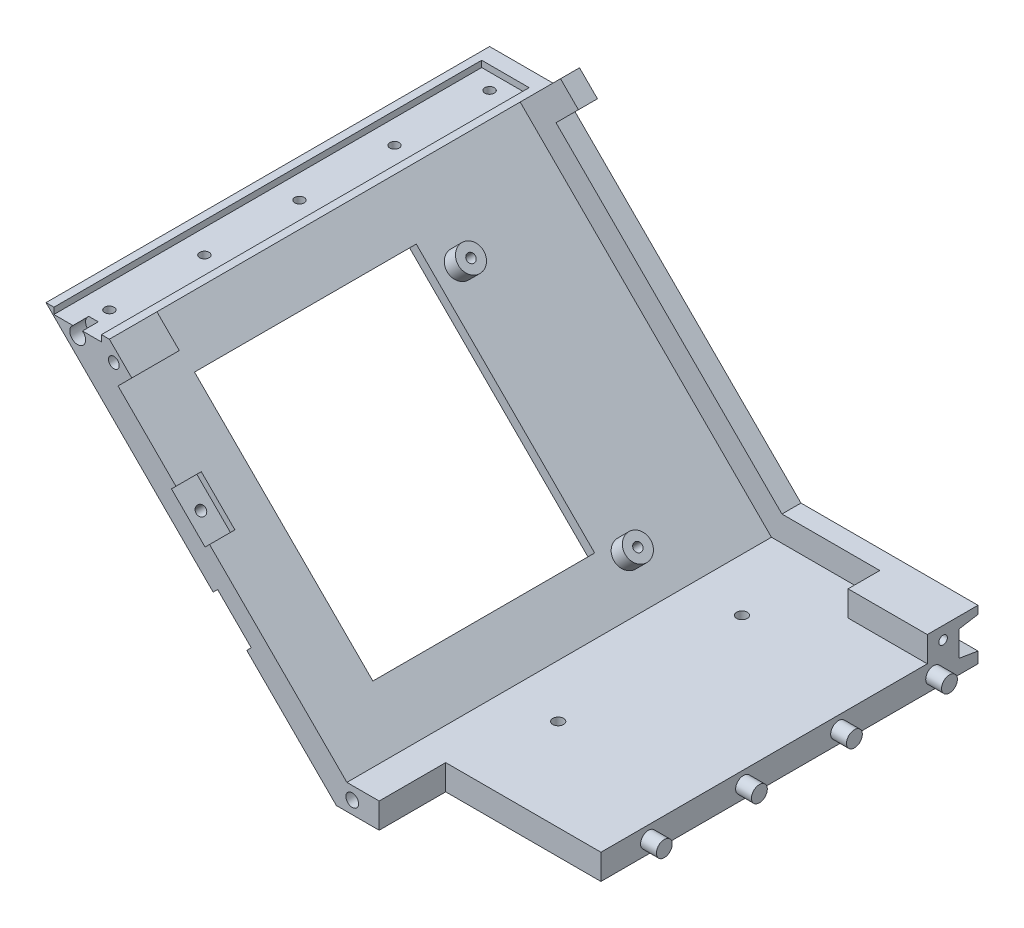
SolidWorks part; units mm, degrees
ref_plane "Plan de face" through (0, 0, 0) normal (0, 0, 1) x (1, 0, 0)
ref_plane "Plan de dessus" through (0, 0, 0) normal (0, 1, 0) x (1, 0, 0)
ref_plane "Plan de droite" through (0, 0, 0) normal (1, 0, 0) x (0, 0, -1)
sketch "Main-Sketch" plane through (0, 0, 0) normal (0, 0, 1) x (1, 0, 0)
  line L0 (0, 0) -> (0, 8)
  line L1 (0, 8) -> (-59.1863, 8)
  line L2 (-59.1863, 8) -> (-138.4931, 87.3069)
  line L3 (-154.15, 91.65) -> (-134.15, 91.65)
  line L4 (-154.15, 91.65) -> (-62.5, 0)
  line L5 (-62.5, 0) -> (0, 0)
  line L8 (-134.15, 91.65) -> (-138.4931, 87.3069)
  dimension "D1" = 8
  dimension "D2" = 8
  dimension "D3" = 62.5
  dimension "D4" = 135
  dimension "D5" = 20
  dimension "D6" = 154.15
extrude "Main-Extrusion" add sketch "Main-Sketch" along normal blind 140
sketch "Lcd-Sketch" plane through (0, 0, 0) normal (0, -1, 0) x (1, 0, 0)
  line L1 (0, 140) -> (-49, 140)
  line L2 (0, 140) -> (0, 119)
  line L3 (0, 119) -> (-49, 119)
  line L4 (-49, 140) -> (-49, 119)
  dimension "D1" = 21
  dimension "D2" = 49
extrude "Lcd-Hole" cut sketch "Lcd-Sketch" against normal through all
sketch "MotorBoard-Hole-Sketch" plane through (-31.25, -31.25, 0) normal (-0.7071, -0.7071, 0) x (0, 0, 1)
  line L0 (0, 173.8068) -> (0, 44.1942) construction
  line L1 (120, 143.8068) -> (50, 143.8068)
  line L2 (120, 143.8068) -> (120, 64.1942)
  line L3 (120, 64.1942) -> (50, 64.1942)
  line L4 (50, 143.8068) -> (50, 64.1942)
  line L5 (140, 173.8068) -> (140, 44.1942) construction
  line L6 (140, 173.8068) -> (0, 173.8068) construction
  line L7 (140, 44.1942) -> (0, 44.1942) construction
  dimension "D1" = 50
  dimension "D2" = 20
  dimension "D3" = 30
  dimension "D4" = 20
extrude "MotorBoard-Hole" cut sketch "MotorBoard-Hole-Sketch" against normal through all
sketch "MotorBoard-Window-Sketch" plane through (-31.25, -31.25, 0) normal (-0.7071, -0.7071, 0) x (0, 0, 1)
  line L0 (120, 64.1942) -> (120, 143.8068) construction
  line L1 (128, 151.8068) -> (42, 151.8068)
  line L2 (128, 151.8068) -> (128, 56.1942)
  line L3 (128, 56.1942) -> (42, 56.1942)
  line L4 (42, 151.8068) -> (42, 56.1942)
  line L5 (120, 143.8068) -> (50, 143.8068) construction
  line L6 (50, 143.8068) -> (50, 64.1942) construction
  line L7 (50, 64.1942) -> (120, 64.1942) construction
  dimension "D1" = 8
  dimension "D2" = 8
  dimension "D3" = 8
  dimension "D4" = 8
extrude "MotorBoard-Window" cut sketch "MotorBoard-Window-Sketch" against normal blind 5
sketch "MotorBoard-Fix-Sketch" plane through (-25.5931, -25.5931, 0) normal (0.7071, 0.7071, 0) x (0, 0, -1)
  line L0 (-140, 47.5079) -> (-140, 159.6647) construction
  line L1 (-140, 47.5079) -> (0, 47.5079) construction
  circle A0 centre (-42.5, 60.5079) radius 4
  circle A1 centre (-42.5, 135.0079) radius 4
  dimension "D1" = 8
  dimension "D2" = 74.5
  dimension "D3" = 97.5
  dimension "D4" = 13
extrude "MotorBoard-Fix-Extrusion" add sketch "MotorBoard-Fix-Sketch" along normal blind 5
sketch "MotorBoard-Fix-Hole-Sketch" plane through (-22.0576, -22.0576, 0) normal (0.7071, 0.7071, 0) x (0, 0, -1)
  circle A0 centre (-42.5, 60.5079) radius 1.35
  circle A1 centre (-42.5, 135.0079) radius 1.35
  circle A2 centre (-42.5, 135.0079) radius 4 construction
  dimension "D1" = 2.7
extrude "MotorBoard-Fix-Hole" cut sketch "MotorBoard-Fix-Hole-Sketch" against normal through all
hole_wizard "Fraisage pour vis à tête fraisée M32" positions "Esquisse8" profile "Esquisse9" countersink size "M3" standard "Ansi Metric" end condition through all
sketch "Esquisse8" plane through (0, 0, 0) normal (0, -1, 0) x (-1, 0, 0)
  line L2 (62.5, -140) -> (49, -140) construction
  line L4 (62.5, -140) -> (62.5, 0) construction
  line L5 (0, -119) -> (0, 0) construction
  point P0 (42.5, -90)
  point P2 (42.5, -32)
  dimension "D1" = 58
  dimension "D2" = 20
  dimension "D3" = 50
  dimension "D4" = 42.5
sketch "Esquisse9" plane through (-42.5, 0, 90) normal (1, 0, 0) x (0, 0, -1)
  line L0 (0, 0) -> (0, 91.65)
  line L1 (0, 91.65) -> (1.7, 91.65)
  line L2 (1.7, 91.65) -> (1.7, 1.45)
  line L3 (1.7, 1.45) -> (3.15, 0)
  line L5 (3.15, 0) -> (0, 0)
  line L6 (-1.7, 1.45) -> (-3.15, 0) construction
  line L11 (0, -6.35) -> (0, 107.95) construction
  dimension "Diamètre du perçage jusqu'au prochain" = 3.4
  dimension "Profondeur du perçage jusqu'au prochain" = 91.65
  dimension "Diamètre du fraisage entrant" = 6.3
  dimension "Angle du fraisage entrant" = 90
sketch "Bottom-Reinforcement-Sketch" plane through (0, 0, 0) normal (0, 0, -1) x (-1, 0, 0)
  line L0 (0, 8) -> (0, 16)
  line L1 (0, 16) -> (55.8726, 16)
  line L2 (55.8726, 16) -> (127.1794, 87.3069)
  line L3 (127.1794, 87.3069) -> (120.1084, 94.3779)
  line L4 (120.1084, 94.3779) -> (125.7652, 100.0348)
  line L5 (125.7652, 100.0348) -> (138.4931, 87.3069)
  line L6 (138.4931, 87.3069) -> (59.1863, 8)
  line L7 (59.1863, 8) -> (0, 8)
  dimension "D1" = 8
  dimension "D2" = 8
  dimension "D3" = 10
  dimension "D4" = 8
extrude "Bottom-Reinforcement-Extrusion" add sketch "Bottom-Reinforcement-Sketch" against normal blind 6 separate body
sketch "LeftFix-Sketch" plane through (0, 0, 0) normal (1, 0, 0) x (0, 0, -1)
  line L0 (0, 0) -> (0, 8) construction
  line L1 (-119, 8) -> (-119, 0) construction
  circle A0 centre (-104, 4) radius 2.5
  point P4 (0, 4)
  dimension "D2" = 5
  dimension "D1" = 15
extrude "LeftFix-Extrusion" add sketch "LeftFix-Sketch" along normal blind 5
pattern_linear "Répétition linéaire1" count 4 spacing 30 along (0, 0, -1) of "LeftFix-Extrusion"
ref_plane "EndOfBottomFix-Plan" through (-15, 0, 0) normal (1, 0, 0) x (0, 0, -1)
ref_axis "EndOfBottomFix-Axe" through (-15, 8, 6) along (0, 1, 0)
ref_plane "EndOfBottomFix-Inclined-Plan" through (-15.4952, 0, 4.1519) normal (0.9659, 0, -0.2588) x (0, 1, 0)
sketch "EndOfBottomFix-Sketch" plane through (0, 0, 0) normal (1, 0, 0) x (0, 0, -1)
  line L0 (0, 3.5) -> (-6, 4.5)
  line L1 (0, 16) -> (0, 8) construction
  line L2 (-6, 4.5) -> (-6, 12.5)
  line L3 (-6, 12.5) -> (0, 13.5)
  line L4 (0, 13.5) -> (0, 3.5)
  line L5 (-6, 16) -> (-6, 8) construction
  dimension "D1" = 2.5
  dimension "D2" = 10
  dimension "D3" = 8
extrude "EndOfBottomFix-Hole" cut sketch "EndOfBottomFix-Sketch" against normal up to surface (16.6077 mm away) up to plane "EndOfBottomFix-Inclined-Plan"
sketch "Bottom-Fix-Reinforcement-Sketch" plane through (0, 8, 0) normal (0, 1, 0) x (1, 0, 0)
  line L1 (0, -6) -> (-25, -6)
  line L2 (0, -6) -> (0, -16)
  line L3 (0, -16) -> (-25, -16)
  line L4 (-25, -6) -> (-25, -16)
  dimension "D1" = 25
  dimension "D2" = 10
extrude "Bottom-Fix-Reinforcement-Extrusion" add sketch "Bottom-Fix-Reinforcement-Sketch" along normal up to surface (8 mm away) up to face at (-27.9363, 16, 3)
sketch "Bottom-Fix-Left-Right-Sketch" plane through (-25, 0, 0) normal (1, 0, 0) x (0, 0, -1)
  line L0 (-16, 16) -> (-16, 8) construction
  line L1 (-6, 16) -> (-16, 16) construction
  circle A0 centre (-11, 12) radius 1.35
  point P4 (-16, 12)
  point P8 (-11, 16)
  dimension "D1" = 2.7
extrude "Bottom-Fix-Left-Right-Hole" cut sketch "Bottom-Fix-Left-Right-Sketch" along normal through all
sketch "Bottom-Top-Fix-Sketch" plane through (0, 0, 140) normal (0, 0, 1) x (1, 0, 0)
  line L1 (-49, 8) -> (-49, 0) construction
  line L2 (-134.15, 91.65) -> (-154.15, 91.65) construction
  circle A0 centre (-57.5, 4) radius 2
  circle A1 centre (-144.15, 87.65) radius 2.5
  point P13 (-49, 4)
  dimension "D1" = 4
  dimension "D3" = 5
  dimension "D2" = 5
  dimension "D4" = 4
  dimension "D5" = 10
extrude "Bottom-Top-Fix-Hole" cut sketch "Bottom-Top-Fix-Sketch" against normal blind 5
sketch "Upp-Fix-Sketch" plane through (0, 0, 140) normal (0, 0, 1) x (1, 0, 0)
  line L0 (-134.15, 91.65) -> (-138.4931, 87.3069)
  line L1 (-138.4931, 87.3069) -> (-131.4221, 80.2358)
  line L2 (-59.1863, 8) -> (-138.4931, 87.3069) construction
  line L3 (-131.4221, 80.2358) -> (-127.0789, 84.5789)
  line L4 (-127.0789, 84.5789) -> (-134.15, 91.65)
  dimension "D1" = 10
extrude "Up-Fix-Extrusion" add sketch "Upp-Fix-Sketch" against normal blind 15
hole_wizard "Fraisage pour vis à tête fraisée M31" positions "Esquisse7" profile "Esquisse6" countersink size "M3" standard "Ansi Metric" end condition up to next
sketch "Esquisse7" plane through (0, 0, 125) normal (0, 0, -1) x (-1, 0, 0)
  line L0 (127.0789, 84.5789) -> (134.15, 91.65) construction
  line L1 (131.4221, 80.2358) -> (127.0789, 84.5789) construction
  point P0 (132.7358, 85.9931)
  dimension "D1" = 3
  dimension "D2" = 5
sketch "Esquisse6" plane through (-132.7358, 85.9931, 125) normal (1, 0, 0) x (0, 1, 0)
  line L0 (0, 0) -> (0, 15)
  line L1 (0, 15) -> (1.7, 15)
  line L2 (1.7, 15) -> (1.7, 1.3)
  line L3 (1.7, 1.3) -> (3, 0)
  line L5 (3, 0) -> (0, 0)
  line L6 (-1.7, 1.3) -> (-3, 0) construction
  line L11 (0, -6.35) -> (0, 107.95) construction
  dimension "Diamètre du perçage jusqu'au prochain" = 3.4
  dimension "Profondeur du perçage jusqu'au prochain" = 15
  dimension "Diamètre du fraisage entrant" = 6
  dimension "Angle du fraisage entrant" = 90
sketch "Reinforcement-Left-Sketch" plane through (0, 91.65, 0) normal (0, 1, 0) x (1, 0, 0)
  line L0 (-154.15, -140) -> (-154.15, 0) construction
  line L1 (-136.65, -140) -> (-151.65, -140)
  line L2 (-136.65, -140) -> (-136.65, -5)
  line L3 (-136.65, -5) -> (-151.65, -5)
  line L4 (-151.65, -140) -> (-151.65, -5)
  line L8 (-134.15, 0) -> (-154.15, 0) construction
  line L9 (-134.15, -140) -> (-154.15, -140) construction
  dimension "D1" = 2.5
  dimension "D2" = 15
  dimension "D4" = 5
extrude "Reinforcement-Left-Hole" cut sketch "Reinforcement-Left-Sketch" against normal blind 2
sketch "Reinforcement-Left-Fix-Sketch" plane through (0, 89.65, 0) normal (0, 1, 0) x (1, 0, 0)
  line L6 (-136.65, -140) -> (-136.65, -5) construction
  line L7 (-142.65, -140) -> (-136.65, -140) construction
  circle A0 centre (-144.15, -130) radius 1.5
  dimension "D1" = 7.5
  dimension "D3" = 3
  dimension "D2" = 10
extrude "Reinforcement-Left-Fix-Hole" cut sketch "Reinforcement-Left-Fix-Sketch" against normal blind 6
pattern_linear "Reinforcement-Left-Fix-Linear-Repeat" count 5 spacing 30 along (0, 0, -1) of "Reinforcement-Left-Fix-Hole"
sketch "Reinforcement-Internal-Sketch" plane through (-25.5931, -25.5931, 0) normal (0.7071, 0.7071, 0) x (0, 0, -1)
  line L0 (-140, 47.5079) -> (-140, 149.6647) construction
  line L1 (-132, 108.8068) -> (-140, 108.8068)
  line L2 (-132, 108.8068) -> (-132, 123.8068)
  line L3 (-132, 123.8068) -> (-140, 123.8068)
  line L4 (-140, 108.8068) -> (-140, 123.8068)
  line L6 (-140, 173.8068) -> (0, 173.8068) construction
  dimension "D1" = 15
  dimension "D2" = 8
  dimension "D3" = 50
extrude "Reinforcement-Internal-Hole" cut sketch "Reinforcement-Internal-Sketch" against normal blind 2
sketch "Reinforcement-Internal-Fix-Sketch" plane through (-27.0074, -27.0074, 0) normal (0.7071, 0.7071, 0) x (0, 0, -1)
  line L0 (-132, 123.8068) -> (-140, 123.8068) construction
  line L1 (-132, 108.8068) -> (-132, 123.8068) construction
  circle A0 centre (-136, 116.3068) radius 1.5
  point P5 (-136, 123.8068)
  point P9 (-132, 116.3068)
  dimension "D1" = 3
extrude "Reinforcement-Internal-Fix-Hole" cut sketch "Reinforcement-Internal-Fix-Sketch" against normal blind 5
sketch "Reinforcement-External-Sketch" plane through (-31.25, -31.25, 0) normal (-0.7071, -0.7071, 0) x (0, 0, 1)
  line L0 (140, 173.8068) -> (140, 44.1942) construction
  line L1 (140, 99.1942) -> (132, 99.1942)
  line L2 (140, 99.1942) -> (140, 84.1942)
  line L3 (140, 84.1942) -> (132, 84.1942)
  line L4 (132, 99.1942) -> (132, 84.1942)
  line L5 (140, 44.1942) -> (0, 44.1942) construction
  point P6 (136, 84.1942)
  dimension "D1" = 15
  dimension "D2" = 40
  dimension "D3" = 8
extrude "Reinforcement-External-Hole" cut sketch "Reinforcement-External-Sketch" against normal blind 2
sketch "Reinforcement-External-Fix-Sketch" plane through (-29.8358, -29.8358, 0) normal (-0.7071, -0.7071, 0) x (0, 0, 1)
  line L0 (140, 84.1942) -> (140, 99.1942) construction
  line L1 (140, 99.1942) -> (132, 99.1942) construction
  circle A0 centre (136, 91.6942) radius 1.5
  point P4 (140, 91.6942)
  point P8 (136, 99.1942)
  dimension "D1" = 3
extrude "Reinforcement-External-Fix-Hole" cut sketch "Reinforcement-External-Fix-Sketch" against normal blind 5
